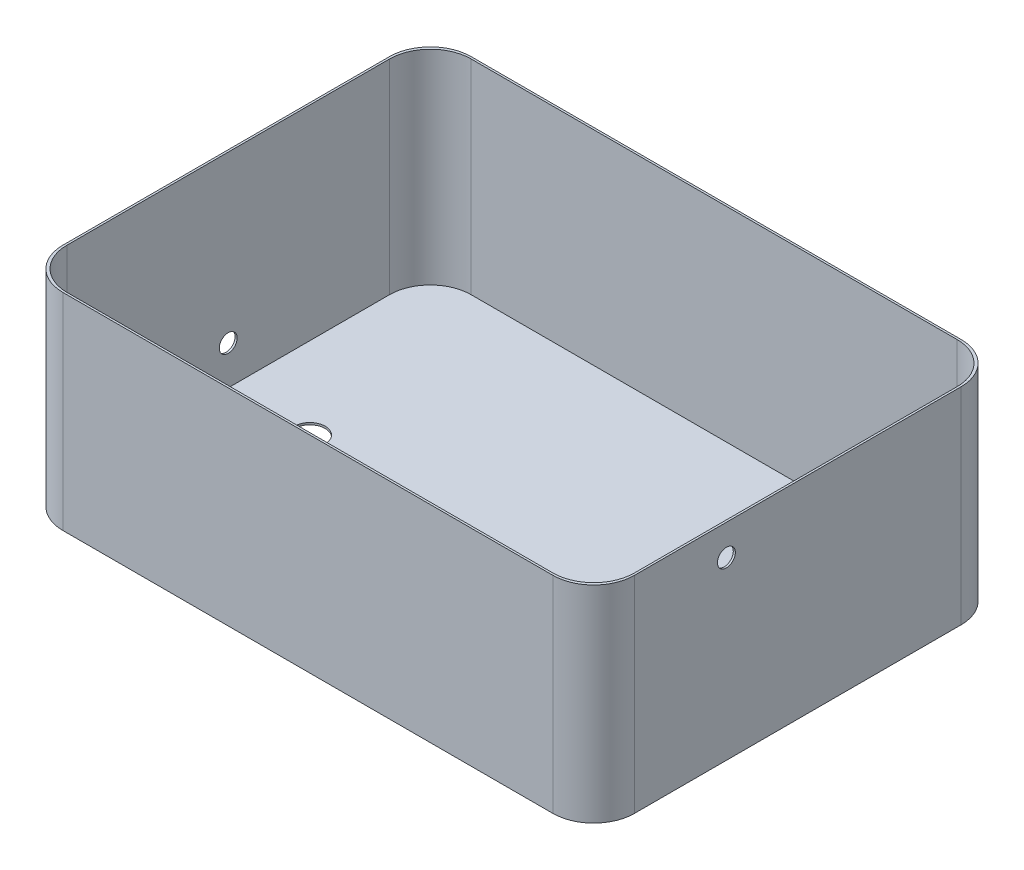
SolidWorks part; units mm, degrees
ref_plane "Front Plane" through (0, 0, 0) normal (0, 0, 1) x (1, 0, 0)
ref_plane "Top Plane" through (0, 0, 0) normal (0, 1, 0) x (1, 0, 0)
ref_plane "Right Plane" through (0, 0, 0) normal (1, 0, 0) x (0, 0, -1)
sketch "Sketch1" plane through (0, 0, 0) normal (0, 1, 0) x (1, 0, 0)
  line L1 (-355.6, -254) -> (355.6, -254)
  line L2 (-355.6, -254) -> (-355.6, 254)
  line L3 (-355.6, 254) -> (355.6, 254)
  line L4 (355.6, -254) -> (355.6, 254)
  line L5 (-355.6, -254) -> (355.6, 254) construction
  line L6 (-355.6, 254) -> (355.6, -254) construction
  line L7 (-353.06, -251.46) -> (353.06, -251.46)
  line L8 (-353.06, -251.46) -> (-353.06, 251.46)
  line L9 (-353.06, 251.46) -> (353.06, 251.46)
  line L10 (353.06, -251.46) -> (353.06, 251.46)
  line L11 (-353.06, -251.46) -> (353.06, 251.46) construction
  line L12 (-353.06, 251.46) -> (353.06, -251.46) construction
  point P0 (0, 0)
  point P6 (0, 0)
  dimension "D1" = 508
  dimension "D2" = 711.2
  dimension "D3" = 2.54
  dimension "D4" = 2.54
extrude "Boss-Extrude1" add sketch "Sketch1" along normal blind 254
sketch "Sketch2" plane through (0, 0, 0) normal (0, -1, 0) x (1, 0, 0)
  line L1 (355.6, 254) -> (-355.6, 254)
  line L2 (355.6, 254) -> (355.6, -254)
  line L3 (355.6, -254) -> (-355.6, -254)
  line L4 (-355.6, 254) -> (-355.6, -254)
  line L5 (355.6, 254) -> (-355.6, -254) construction
  line L6 (355.6, -254) -> (-355.6, 254) construction
  point P0 (0, 0)
extrude "Boss-Extrude2" add sketch "Sketch2" along normal blind 2.54
fillet "Fillet1" radius 50.8 8 edges at (353.06, 127, 251.46) (-353.06, 127, 251.46) (-353.06, 127, -251.46) (353.06, 127, -251.46) (355.6, 125.73, -254) (355.6, 125.73, 254) (-355.6, 125.73, 254) (-355.6, 125.73, -254)
sketch "Sketch5" plane through (0, 0, 0) normal (0, 1, 0) x (1, 0, 0)
  line L0 (-353.06, 200.66) -> (-353.06, -200.66) construction
  line L1 (302.26, 251.46) -> (-302.26, 251.46) construction
  circle A0 centre (-251.46, 0) radius 19.05
  dimension "D3" = 38.1
  dimension "D1" = 101.6
  dimension "D2" = 251.46
extrude "Cut-Extrude1" cut sketch "Sketch5" against normal blind 2.54
hole_wizard "7/8 (0.875) Diameter Hole1" positions "Sketch6" profile "Sketch7" hole size "7/8" standard "ANSI Inch" end condition up to next
sketch "Sketch6" plane through (-355.6, 0, 0) normal (-1, 0, 0) x (0, 0, 1)
  line L0 (203.2, -2.54) -> (-203.2, -2.54) construction
  line L1 (203.2, -2.54) -> (203.2, 254) construction
  point P0 (0, 48.26)
  dimension "D1" = 50.8
  dimension "D2" = 203.2
sketch "Sketch7" plane through (-355.6, 48.26, 0) normal (0, 1, 0) x (0, 0, 1)
  line L0 (0, 0) -> (0, 2.54)
  line L1 (0, 2.54) -> (11.1125, 2.54)
  line L2 (11.1125, 2.54) -> (11.1125, 0)
  line L5 (11.1125, 0) -> (0, 0)
  line L11 (0, -6.35) -> (0, 107.95) construction
  dimension "Thru Hole Dia." = 22.225
  dimension "Thru Hole Depth" = 2.54
hole_wizard "7/8 (0.875) Diameter Hole2" positions "Sketch8" profile "Sketch9" hole size "7/8" standard "ANSI Inch" end condition up to next
sketch "Sketch8" plane through (355.6, 0, 0) normal (1, 0, 0) x (0, 0, -1)
  line L0 (-203.2, 254) -> (203.2, 254) construction
  line L1 (0, -2.54) -> (0, 254) construction
  line L2 (203.2, -2.54) -> (-203.2, -2.54) construction
  point P0 (-88.9, 215.9)
  dimension "D1" = 38.1
  dimension "D2" = 88.9
sketch "Sketch9" plane through (355.6, 215.9, 88.9) normal (0, 1, 0) x (0, 0, -1)
  line L0 (0, 0) -> (0, 2.54)
  line L1 (0, 2.54) -> (11.1125, 2.54)
  line L2 (11.1125, 2.54) -> (11.1125, 0)
  line L5 (11.1125, 0) -> (0, 0)
  line L11 (0, -6.35) -> (0, 107.95) construction
  dimension "Thru Hole Dia." = 22.225
  dimension "Thru Hole Depth" = 2.54
